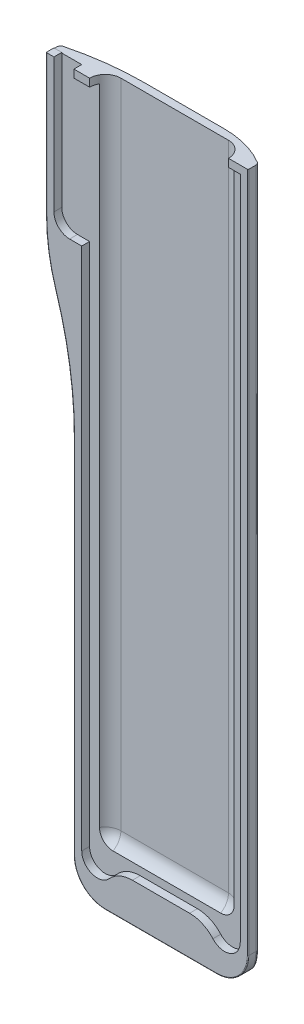
SolidWorks part; units mm, degrees
material "Сплав 2024"
ref_plane "Спереди" through (0, 0, 0) normal (0, 0, 1) x (1, 0, 0)
ref_plane "Сверху" through (0, 0, 0) normal (0, 1, 0) x (1, 0, 0)
ref_plane "Справа" through (0, 0, 0) normal (1, 0, 0) x (0, 0, -1)
sketch "Эскиз1" plane through (0, 0, 0) normal (0, 0, 1) x (1, 0, 0)
  line L0 (2, 143.8533) -> (-1.1, 143.8533)
  line L1 (-5.1, 147.8533) -> (-5.1, 182.1367)
  line L2 (-5.1, 182.1367) -> (-7.1, 182.1367)
  line L3 (-7.1, 182.1367) -> (-7.1, 146)
  line L4 (0, 100.3975) -> (0, 8)
  line L5 (8, 0) -> (36.5, 0)
  line L6 (44.5, 8) -> (44.5, 182)
  line L7 (44.5, 182) -> (0, 182)
  line L8 (0, 182) -> (0, 180)
  line L9 (0, 180) -> (42.5, 180)
  line L10 (42.5, 180) -> (42.5, 10)
  line L11 (29.5557, 10) -> (14.9443, 10)
  line L12 (2, 10) -> (2, 143.8533)
  arc A0 (-5.1, 147.8533) -> (-1.1, 143.8533) centre (-1.1, 147.8533) ccw
  arc A1 (-7.1, 146) -> (-4.7333, 130.7992) centre (42.9, 146) ccw
  arc A2 (0, 100.3975) -> (-4.7333, 130.7992) centre (-100, 100.3975) ccw
  arc A3 (0, 8) -> (8, 0) centre (8, 8) ccw
  arc A4 (36.5, 0) -> (44.5, 8) centre (36.5, 8) ccw
  arc A5 (35.5186, 7.3333) -> (42.5, 10) centre (38.5, 10) ccw
  arc A6 (35.5186, 7.3333) -> (29.5557, 10) centre (29.5557, 2) ccw
  arc A7 (14.9443, 10) -> (8.9814, 7.3333) centre (14.9443, 2) ccw
  arc A8 (2, 10) -> (8.9814, 7.3333) centre (6, 10) ccw
extrude "Бобышка-Вытянуть1" add sketch "Эскиз1" along normal blind 2
sketch "Эскиз2" plane through (0, 0, 2) normal (0, 0, 1) x (1, 0, 0)
  line L0 (-7.1, 182.1367) -> (-7.1, 146) construction
  line L1 (0, 100.3975) -> (0, 8) construction
  line L2 (8, 0) -> (36.5, 0) construction
  line L3 (44.5, 8) -> (44.5, 182) construction
  line L4 (44.5, 182) -> (0, 182) construction
  line L5 (-7.1, 182) -> (-7.1, 146)
  line L6 (0, 100.3975) -> (0, 8)
  line L7 (8, 0) -> (36.5, 0)
  line L8 (44.5, 8) -> (44.5, 182)
  line L9 (44.5, 182) -> (0, 182)
  line L10 (0, 182) -> (-7.1, 182)
  arc A0 (-7.1, 146) -> (-4.7333, 130.7992) centre (42.9, 146) ccw construction
  arc A1 (0, 100.3975) -> (-4.7333, 130.7992) centre (-100, 100.3975) ccw construction
  arc A2 (0, 8) -> (8, 0) centre (8, 8) ccw construction
  arc A3 (36.5, 0) -> (44.5, 8) centre (36.5, 8) ccw construction
  arc A4 (-7.1, 146) -> (-4.7333, 130.7992) centre (42.9, 146) ccw
  arc A5 (0, 100.3975) -> (-4.7333, 130.7992) centre (-100, 100.3975) ccw
  arc A6 (0, 8) -> (8, 0) centre (8, 8) ccw
  arc A7 (36.5, 0) -> (44.5, 8) centre (36.5, 8) ccw
extrude "Бобышка-Вытянуть2" add sketch "Эскиз2" along normal blind 4
sketch "Эскиз3" plane through (0, 0, 0) normal (0, 1, 0) x (1, 0, 0)
  line L0 (44.5, -6) -> (-7.1, -6) construction
  line L1 (44.5, -6) -> (44.5, 0) construction
  line L2 (44.5, -2.5329) -> (44.5, -6)
  line L3 (44.5, -6) -> (32.5, -6)
  line L4 (22.25, -6) -> (22.25, -8.3952) construction
  line L5 (8, -6) -> (36.5, -6) construction
  line L6 (12, -6) -> (-7.1, -6)
  line L7 (-7.1, -6) -> (-7.1, -3.47)
  line L8 (0, -6) -> (0, 0) construction
  arc A0 (32.5, -6) -> (44.5, -2.5329) centre (32.5, 16.5) ccw
  arc A1 (-7.1, -3.47) -> (12, -6) centre (12, 67.3618) ccw
  point P4 (44.5, -3)
  dimension "D1" = 45
  dimension "D3" = 2.53
  dimension "D2" = 12
  dimension "D4" = 12
extrude "Вырез-Вытянуть1" cut sketch "Эскиз3" along normal through all
sketch "Эскиз4" plane through (0, 0, 2) normal (0, 0, -1) x (-1, 0, 0)
  line L0 (-39.5, 182.015) -> (-39.5, 12)
  line L1 (-39.5, 12) -> (-4, 12)
  line L2 (-4, 12) -> (-4, 182.015)
  line L3 (-4, 182.015) -> (-39.5, 182.015)
  line L4 (-42.5, 180) -> (-42.5, 10) construction
  line L5 (-2, 10) -> (-2, 143.8533) construction
  line L6 (-29.5557, 10) -> (-14.9443, 10) construction
  dimension "D1" = 3
  dimension "D2" = 2
  dimension "D3" = 2
extrude "Вырез-Вытянуть2" cut sketch "Эскиз4" against normal blind 2 and the other way up to next
fillet "Скругление2" radius 4 1 edges at (21.75, 12, 4)
fillet "Скругление4" radius 4 4 edges at (4, 13.4641, 3.4641) (39.5, 13.4641, 3.4641) (4, 98.7321, 4) (39.5, 98.7321, 4)
mirror "Зеркальное отражение2" about plane through (-1.1, 147.8533, 0) normal (0, 0, 1) of "Бобышка-Вытянуть2", "Бобышка-Вытянуть1", "Вырез-Вытянуть1", "Вырез-Вытянуть2", "Скругление2", "Скругление4"
sketch "Эскиз5" plane through (0, 0, 6) normal (0, 0, 1) x (1, 0, 0)
  line L1 (-11.0217, -6.3899) -> (60.3907, -6.3899)
  line L2 (-11.0217, -6.3899) -> (-11.0217, 200.8815)
  line L3 (-11.0217, 200.8815) -> (60.3907, 200.8815)
  line L4 (60.3907, -6.3899) -> (60.3907, 200.8815)
extrude "Вырез-Вытянуть3" cut sketch "Эскиз5" against normal blind 6
fillet "Скругление5" radius 1 10 edges at (-7.1, 164, -3.47) (44.5, 95, -2.5329) (41.4475, 1.7134, -4.1444) (34.508, 0, -5.9102) (22.25, 0, -6) (9.9993, 0, -5.9727) (1.7195, 3.0446, -5.2761) (0, 54.1987, -5.0119)
fillet "Скругление6" radius 0.2 8 edges at (-7.1, 164.0683, 0) (-6.5048, 138.308, 0) (-1.1904, 115.7815, 0) (0, 54.1987, 0) (2.3431, 2.3431, 0) (22.25, 0, 0) (42.1569, 2.3431, 0) (44.5, 95, 0)
